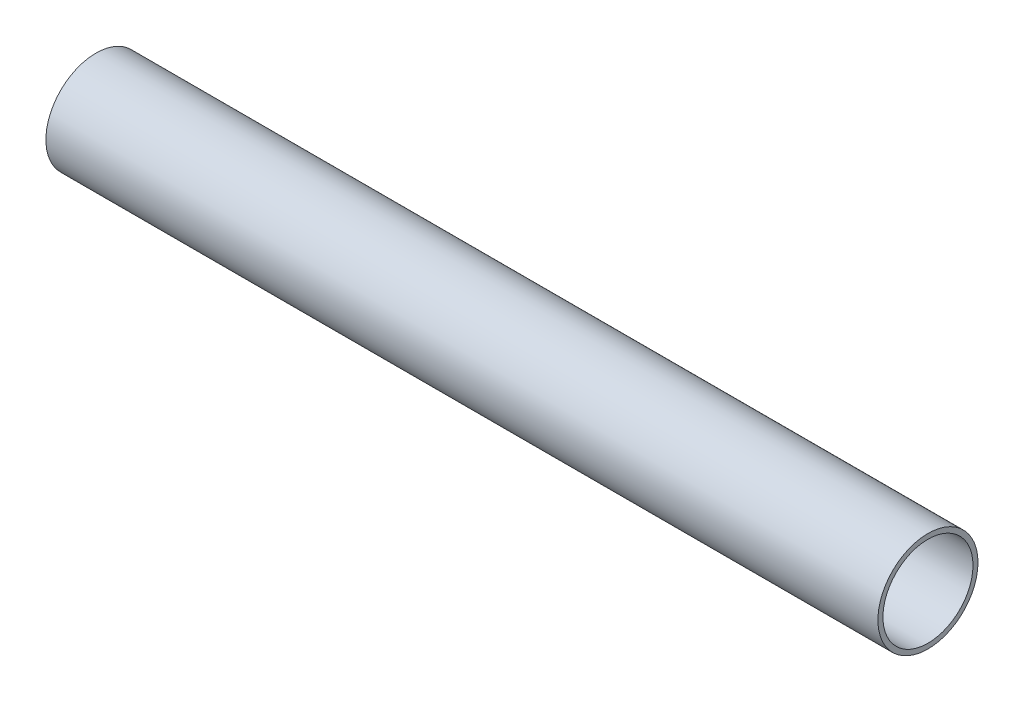
SolidWorks part; units mm, degrees
material "PC High Viscosity"
ref_plane "Front Plane" through (0, 0, 0) normal (0, 0, 1) x (1, 0, 0)
ref_plane "Top Plane" through (0, 0, 0) normal (0, 1, 0) x (1, 0, 0)
ref_plane "Right Plane" through (0, 0, 0) normal (1, 0, 0) x (0, 0, -1)
sketch "Sketch1" plane through (0, 0, 0) normal (1, 0, 0) x (0, 0, -1)
  circle A0 centre (0, 0) radius 15.875
  dimension "D1" = 31.75
extrude "Extrude-Thin1" add sketch "Sketch1" along normal mid plane 263.9115 thin thin type one direction reverse wall 1.5875
sketch "Sketch2" plane through (0, 0, 0) normal (0, 1, 0) x (1, 0, 0)
  line L0 (131.9557, 15.875) -> (-131.9557, 15.875) construction
  line L1 (-102.8953, 15.875) -> (-116.4111, 15.875)
  line L2 (-102.8953, 15.875) -> (-102.8953, -15.875)
  line L3 (-102.8953, -15.875) -> (-116.4111, -15.875)
  line L4 (-116.4111, 15.875) -> (-116.4111, -15.875)
  line L5 (-131.9557, -15.875) -> (131.9557, -15.875) construction
  line L6 (-131.9557, 14.2875) -> (-131.9557, -14.2875) construction
  point P10 (-114.2547, 15.875)
  dimension "D1" = 29.0604
